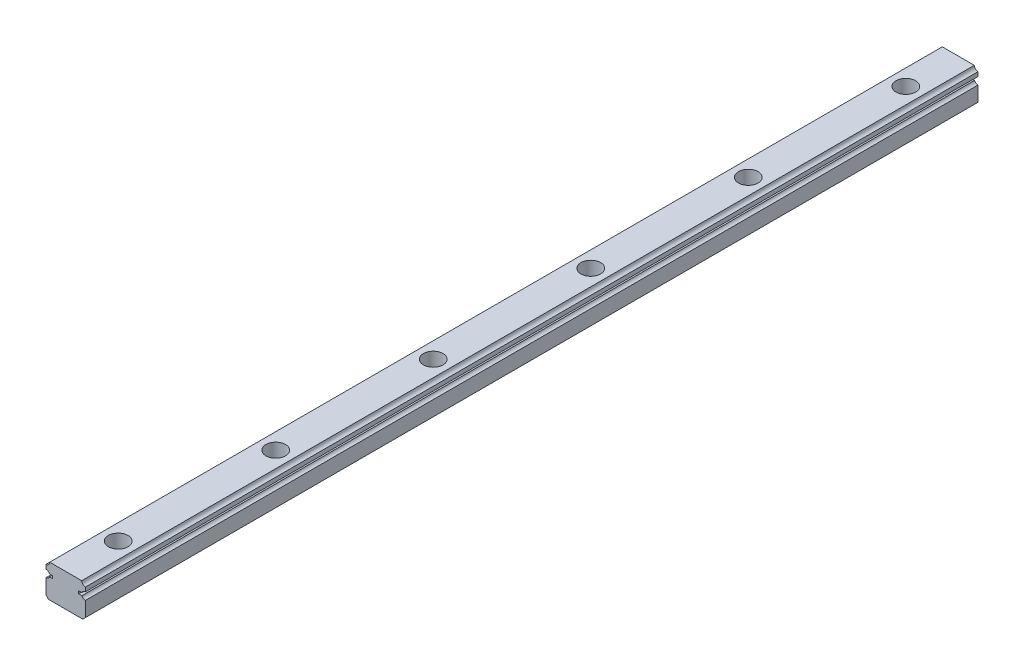
SolidWorks part; units mm, degrees
ref_plane "Front" through (0, 0, 0) normal (0, 0, 1) x (1, 0, 0)
ref_plane "Top" through (0, 0, 0) normal (0, 1, 0) x (1, 0, 0)
ref_plane "Right" through (0, 0, 0) normal (1, 0, 0) x (0, 0, -1)
sketch "15mm" plane through (0, 0, 0) normal (0, 0, 1) x (1, 0, 0)
  line L0 (0, 0) -> (0, 12.5) construction
  line L2 (4.95, 7.6) -> (6.1923, 7.6)
  line L3 (4.95, 8.6) -> (4.95, 7.6)
  line L4 (6.1923, 8.6) -> (4.95, 8.6)
  line L5 (7.5, 11.1) -> (7.5, 9.5)
  line L6 (-6.1, 12.5) -> (6.1, 12.5)
  line L7 (-7.5, 9.5) -> (-7.5, 11.1)
  line L8 (-4.95, 8.6) -> (-6.1923, 8.6)
  line L9 (-4.95, 7.6) -> (-4.95, 8.6)
  line L10 (-6.1923, 7.6) -> (-4.95, 7.6)
  line L11 (-7.5, 1) -> (-7.5, 6.7)
  line L12 (-6.5, 0) -> (-7.5, 1)
  line L13 (6.5, 0) -> (-6.5, 0)
  line L14 (7.5, 1) -> (6.5, 0)
  line L15 (7.5, 6.7) -> (7.5, 1)
  arc A0 (6.1923, 8.6) -> (7.5, 9.5) centre (7.5, 8.1) cw
  arc A1 (7.5, 11.1) -> (6.1, 12.5) centre (7.5, 12.5) cw
  arc A2 (-6.1, 12.5) -> (-7.5, 11.1) centre (-7.5, 12.5) cw
  arc A3 (-7.5, 9.5) -> (-6.1923, 8.6) centre (-7.5, 8.1) cw
  arc A4 (-6.1923, 7.6) -> (-7.5, 6.7) centre (-7.5, 8.1) cw
  arc A5 (7.5, 6.7) -> (6.1923, 7.6) centre (7.5, 8.1) cw
extrude "Extrude1" add sketch "15mm" along normal mid plane 340
sketch "Sketch1" plane through (0, 0, 0) normal (1, 0, 0) x (0, 0, -1)
  line L0 (-150, 0) -> (-150, 12.5) construction
  line L1 (-170, 0) -> (170, 0) construction
  line L2 (-170, 12.5) -> (170, 12.5) construction
  line L3 (-150, 12.5) -> (-146.25, 12.5)
  line L4 (-146.25, 12.5) -> (-146.25, 7.2)
  line L5 (-146.25, 7.2) -> (-147.75, 7.2)
  line L6 (-147.75, 7.2) -> (-147.75, 0)
  line L7 (-147.75, 0) -> (-150, 0)
  line L8 (-150, 0) -> (-150, 12.5)
  line L9 (-170, 1) -> (-170, 6.7) construction
  dimension "D1" = 4.5
  dimension "D2" = 7.5
  dimension "D3" = 5.3
  dimension "D4" = 20
revolve "Cut-Revolve1" cut sketch "Sketch1" angle 360 about L0
sketch "Sketch2" plane through (0, 0, 0) normal (1, 0, 0) x (0, 0, -1)
  line L0 (150, 12.5) -> (150, 0) construction
  line L1 (-170, 12.5) -> (170, 12.5) construction
  line L2 (-170, 0) -> (170, 0) construction
  line L3 (150, 0) -> (152.25, 0)
  line L4 (152.25, 0) -> (152.25, 7.2)
  line L5 (152.25, 7.2) -> (153.75, 7.2)
  line L6 (153.75, 7.2) -> (153.75, 12.5)
  line L7 (153.75, 12.5) -> (150, 12.5)
  line L8 (150, 0) -> (170, 0) construction
  line L9 (-147.75, 0) -> (-150, 0) construction
  line L10 (-150, 12.5) -> (-146.25, 12.5) construction
  line L11 (-170, 0) -> (-150, 0) construction
  line L12 (-146.25, 7.2) -> (-147.75, 7.2) construction
  line L13 (150, 12.5) -> (150, 0)
revolve "Cut-Revolve2" cut sketch "Sketch2" angle 360 about L0
ref_axis "Axis1" through (0, 0, -121) along (0, 0, 1)
pattern_linear "LPattern1" count 5 spacing 60 along (0, 0, 1) of "Cut-Revolve2"
